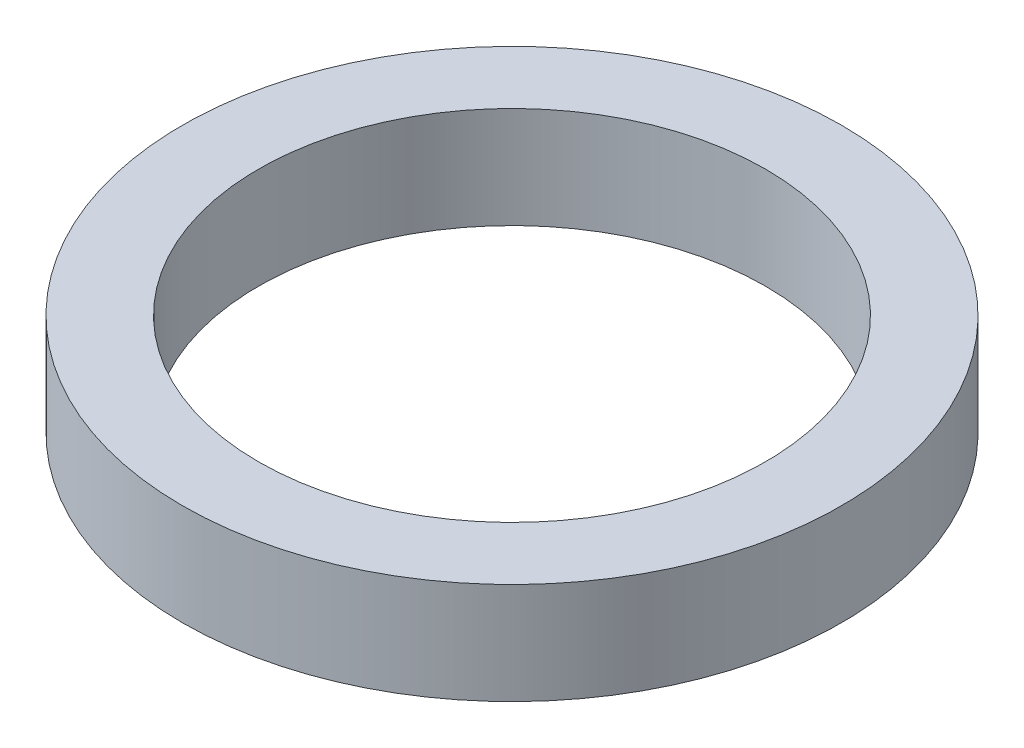
SolidWorks part; units mm, degrees
ref_plane "Front Plane" through (0, 0, 0) normal (0, 0, 1) x (1, 0, 0)
ref_plane "Top Plane" through (0, 0, 0) normal (0, 1, 0) x (1, 0, 0)
ref_plane "Right Plane" through (0, 0, 0) normal (1, 0, 0) x (0, 0, -1)
sketch "Sketch1" plane through (0, 0, 0) normal (0, 1, 0) x (1, 0, 0)
  circle A0 centre (0, 0) radius 3.5
  circle A1 centre (0, 0) radius 2.525
  dimension "D1" = 7
  dimension "D2" = 5.05
extrude "Boss-Extrude1" [suppressed] add sketch "Sketch1" along normal blind 6
sketch "Sketch2" plane through (0, 0, 0) normal (0, 1, 0) x (1, 0, 0)
  circle A0 centre (0, 0) radius 7.5
  circle A1 centre (0, 0) radius 10
  dimension "D1" = 15
  dimension "D2" = 20
extrude "Boss-Extrude2" [suppressed] add sketch "Sketch2" along normal blind 0.5
sketch "Sketch3" plane through (0, 0, 0) normal (0, 1, 0) x (1, 0, 0)
  circle A0 centre (0, 0) radius 5
  circle A1 centre (0, 0) radius 6.5
  dimension "D1" = 10
  dimension "D2" = 13
extrude "Boss-Extrude3" add sketch "Sketch3" along normal blind 2
